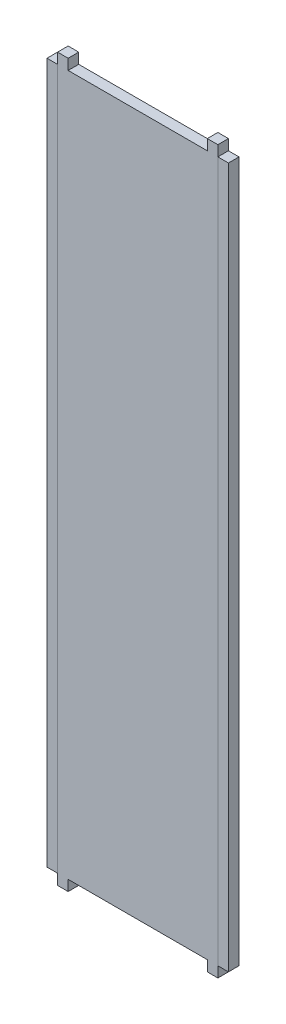
SolidWorks part; units mm, degrees
ref_plane "Front Plane" through (0, 0, 0) normal (0, 0, 1) x (1, 0, 0)
ref_plane "Top Plane" through (0, 0, 0) normal (0, 1, 0) x (1, 0, 0)
ref_plane "Right Plane" through (0, 0, 0) normal (1, 0, 0) x (0, 0, -1)
sketch "Sketch1" plane through (0, 0, 0) normal (0, 0, 1) x (1, 0, 0)
  line L0 (0.9075, 0) -> (-0.9075, 0) construction
  line L1 (-12.5, 56.275) -> (12.5, 56.275)
  line L2 (-12.5, 56.275) -> (-12.5, -56.275)
  line L3 (-12.5, -56.275) -> (12.5, -56.275)
  line L4 (12.5, 56.275) -> (12.5, -56.275)
  line L5 (0, -0.9075) -> (0, 0.9075) construction
  point P6 (12.5, 0)
  point P9 (0, 56.275)
  dimension "D1" = 112.55
  dimension "D2" = 25
extrude "Boss-Extrude1" add sketch "Sketch1" along normal blind 1.65
sketch "Sketch2" plane through (0, 0, 1.65) normal (0, 0, 1) x (1, 0, 0)
  line L0 (12.5, -56.275) -> (12.5, 56.275) construction
  line L1 (12.5, 54.625) -> (14.15, 54.625)
  line L2 (12.5, 54.625) -> (12.5, -54.625)
  line L3 (12.5, -54.625) -> (14.15, -54.625)
  line L4 (14.15, 54.625) -> (14.15, -54.625)
  line L5 (12.5, 56.275) -> (-12.5, 56.275) construction
  line L6 (-12.5, -56.275) -> (12.5, -56.275) construction
  line L7 (0, -0.9075) -> (0, 0.9075) construction
  line L8 (-14.15, 54.625) -> (-14.15, -54.625)
  line L9 (-12.5, -54.625) -> (-14.15, -54.625)
  line L10 (-12.5, 54.625) -> (-12.5, -54.625)
  line L11 (-12.5, 54.625) -> (-14.15, 54.625)
  dimension "D1" = 1.65
  dimension "D2" = 1.65
  dimension "D3" = 1.65
extrude "Boss-Extrude2" add sketch "Sketch2" against normal blind 1.65 separate body
sketch "Sketch3" plane through (0, 56.275, 0) normal (0, 1, 0) x (1, 0, 0)
  line L0 (12.5, 0) -> (-12.5, 0) construction
  line L1 (-10.85, 0) -> (10.85, 0)
  line L2 (-10.85, 0) -> (-10.85, -1.65)
  line L3 (-10.85, -1.65) -> (10.85, -1.65)
  line L4 (10.85, 0) -> (10.85, -1.65)
  line L5 (12.5, -1.65) -> (-12.5, -1.65) construction
  line L6 (12.5, -1.65) -> (12.5, 0) construction
  line L7 (-12.5, -1.65) -> (-12.5, 0) construction
  dimension "D1" = 1.65
  dimension "D2" = 1.65
extrude "Cut-Extrude1" cut sketch "Sketch3" against normal blind 1.65
mirror "Mirror1" about plane through (0, 0, 0) normal (0, 1, 0) of "Cut-Extrude1"
equation "\"Dinoskin scale\"= 1.8"
equation "\"pattern X\"= 3"
equation "\"Pattern Y\"= 9"
equation "\"Base Innerline\"= 0.34"
equation "\"lenght\"= 200"
equation "\"PCB Thickness\"= 1.65"
equation "\"Base Width\"= 4.5"
equation "\"Base Outerline\"= 1"
equation "\"Base Inner to Outer\"= 1"
equation "\"Dinoskin Outerline\"= \"Base Outerline\" * \"Dinoskin scale\""
equation "\"Dinoskin Innerline\"= \"Base Innerline\" * \"Dinoskin scale\""
equation "\"Dinoskin Width\"= \"Base Width\" * \"Dinoskin scale\""
equation "\"Dinoskin Inner to Outer\"= \"Base Inner to Outer\" * \"Dinoskin scale\""
equation "\"Diagonal dist\"= \"Dinoskin Width\" + ( ( \"Dinoskin Innerline\" + \"Dinoskin Outerline\" ) / 2 + \"Dinoskin Inner to Outer\" ) / cos ( 30 )"
equation "\"Dinoskin pattern Y\"= \"Diagonal dist\" * sin ( 30 )"
equation "\"Offset Y\"= 2 * \"Dinoskin pattern Y\""
equation "\"Diagonal dist 2\"= \"Dinoskin Width\" + ( ( \"Dinoskin Innerline\" + \"Dinoskin Outerline\" ) / 2 + 1 ) / cos ( 30 )"
equation "\"Dinoskin pattern X\"= \"Diagonal dist\" * cos ( 30 )"
equation "\"offset x\"= \"Dinoskin pattern X\" * 2"
equation "\"Pattern spacing X\"= \"offset x\" * ( \"pattern X\" - 0.5 ) / 2"
equation "\"Pattern spacing Y\"= \"Offset Y\" *  ( \"Pattern Y\" - 0.5 )  / 2 + 13"
equation "\"offset corner beams\" = 1"
equation "\"D1@Sketch1\"=(\"lenght\" * \"Lenght Ratio\" / 2) * 7 / 8 - 25 - \"PCB Thickness\" - \"lenght\" / 16 + 2.95"
equation "\"D2@Sketch1\"= \"lenght\" / 8"
equation "\"D1@Sketch2\"= \"PCB Thickness\""
equation "\"D2@Sketch2\"=\"PCB Thickness\""
equation "\"D3@Sketch2\"= \"PCB Thickness\""
equation "\"D1@Boss-Extrude2\"=  \"PCB Thickness\""
equation "\"D1@Sketch3\"=\"PCB Thickness\""
equation "\"D2@Sketch3\"=\"PCB Thickness\""
equation "\"D1@Cut-Extrude1\"=\"PCB Thickness\""
equation "\"D8@Sketch3\"=\"Dinoskin Inner to Outer\""
equation "\"D17@Sketch3\"=\"Dinoskin Width\""
equation "\"D6@Sketch3\"=\"Dinoskin Innerline\"/2"
equation "\"D3@Sketch3\"=\"Dinoskin Innerline\"/2"
equation "\"D20@Sketch3\"=\"Dinoskin Outerline\""
equation "\"D19@Sketch3\"=\"Dinoskin Outerline\""
equation "\"D15@Sketch3\"=\"Dinoskin Outerline\"/2"
equation "\"D14@Sketch3\"=\"Dinoskin Outerline\"/2"
equation "\"D10@Sketch3\"=\"Dinoskin Outerline\"/2"
equation "\"D16@Sketch3\"=\"Dinoskin Outerline\"/2"
equation "\"D3@LPattern1\"=\"Dinoskin pattern Y\""
equation "\"D1@Plane1\"=\"PCB Thickness\"/2"
equation "\"D2@LPattern2\"= \"pattern X\""
equation "\"D1@LPattern2\"=\"Pattern Y\""
equation "\"D4@LPattern1\"=\"Dinoskin pattern X\""
equation "\"D3@LPattern2\"= \"Offset Y\""
equation "\"D4@LPattern2\"= \"offset x\""
equation "\"D5@Sketch3\"= \"Pattern spacing X\""
equation "\"D7@Sketch3\"= \"Pattern spacing Y\""
equation "\"D1@Sketch5\"=\"PCB Thickness\""
equation "\"D3@Sketch5\"=\"lenght\" / 64"
equation "\"D5@Sketch5\"= \"offset corner beams\""
equation "\"D6@Sketch5\"=\"offset corner beams\""
equation "\"D1@Sketch6\"= \"lenght\" / 8 + \"PCB Thickness\" * 4"
equation "\"D2@Sketch6\"= \"PCB Thickness\""
equation "\"D3@DinoSkin diagonal pattern\" = \"Dinoskin pattern Y\""
equation "\"D2@Main Dinoskin Array\" = \"pattern X\""
equation "\"D1@Main Dinoskin Array\" = \"Pattern Y\""
equation "\"D4@DinoSkin diagonal pattern\" = \"Dinoskin pattern X\""
equation "\"D3@Main Dinoskin Array\" = \"Offset Y\""
equation "\"D4@Main Dinoskin Array\" = \"offset x\""
equation "\"D1@Sketch8\"=\"PCB Thickness\""
equation "\"D2@Sketch8\"=\"lenght\" / 64"
equation "\"D3@Sketch8\"=\"PCB Thickness\""
equation "\"D4@Sketch8\"= \"lenght\" / 64"
equation "\"D2@Sketch9\"=\"PCB Thickness\""
equation "\"D3@Sketch9\"=\"PCB Thickness\""
equation "\"D4@Sketch6\"=\"PCB Thickness\""
equation "\"D5@Sketch6\"=\"PCB Thickness\""
equation "\"D9@Sketch1\"= \"lenght\" * \"Lenght Ratio\"/2"
equation "\"Lenght Ratio\" = 1.7"
